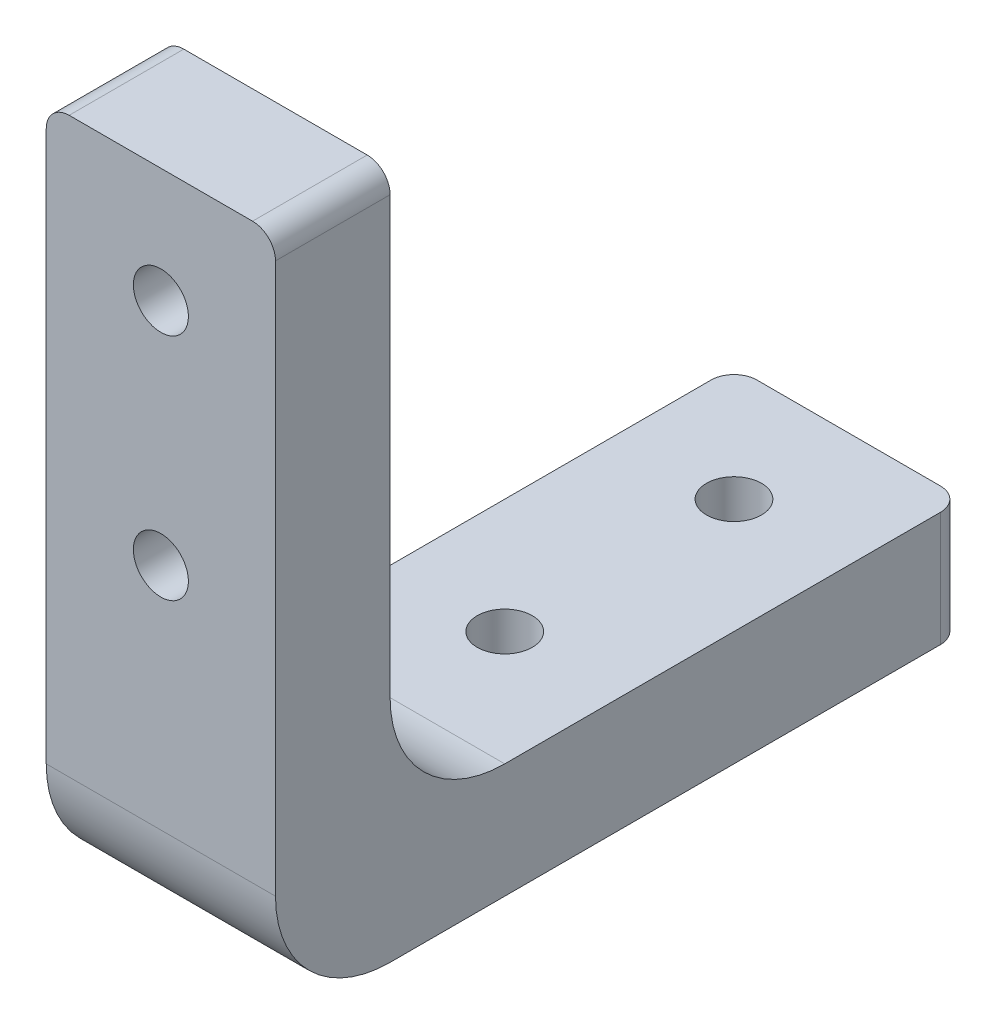
SolidWorks part; units mm, degrees
material "PEI"
ref_plane "Спереди" through (0, 0, 0) normal (0, 0, 1) x (1, 0, 0)
ref_plane "Сверху" through (0, 0, 0) normal (0, 1, 0) x (1, 0, 0)
ref_plane "Справа" through (0, 0, 0) normal (1, 0, 0) x (0, 0, -1)
sketch "Эскиз1" plane through (0, 0, 0) normal (1, 0, 0) x (0, 0, -1)
  line L0 (0, 30) -> (0, 0)
  line L1 (0, 0) -> (30, 0)
  line L2 (30, 0) -> (30, 5)
  line L3 (30, 5) -> (5, 5)
  line L4 (5, 5) -> (5, 30)
  line L5 (5, 30) -> (0, 30)
  dimension "D1" = 30
  dimension "D2" = 30
  dimension "D3" = 5
extrude "Бобышка-Вытянуть1" add sketch "Эскиз1" along normal blind 5 and the other way blind 5
sketch "Эскиз2" plane through (0, 5, 0) normal (0, 1, 0) x (1, 0, 0)
  line L1 (-10.7235, 20) -> (49989.2765, 20) construction
  line L2 (-5, 0) -> (5, 0) construction
  circle A0 centre (0, 25) radius 1.2
  circle A1 centre (0, 15) radius 1.2
  dimension "D1" = 2.4
  dimension "D2" = 15
  dimension "D3" = 5
extrude "Вырез-Вытянуть1" cut sketch "Эскиз2" against normal through all
sketch "Эскиз3" plane through (0, 0, -5) normal (0, 0, -1) x (-1, 0, 0)
  line L0 (5, 30) -> (-5, 30) construction
  line L1 (13.3016, 20) -> (-49986.6984, 20) construction
  circle A0 centre (0, 25) radius 1.2
  circle A1 centre (0, 15) radius 1.2
  dimension "D1" = 2.4
  dimension "D2" = 5
  dimension "D3" = 5
extrude "Вырез-Вытянуть2" cut sketch "Эскиз3" against normal through all
fillet "Скругление1" radius 1 4 edges at (-5, 2.5, -30) (5, 2.5, -30) (5, 30, -2.5) (-5, 30, -2.5)
fillet "Скругление2" radius 5 2 edges at (0, 0, 0) (0, 5, -5)
